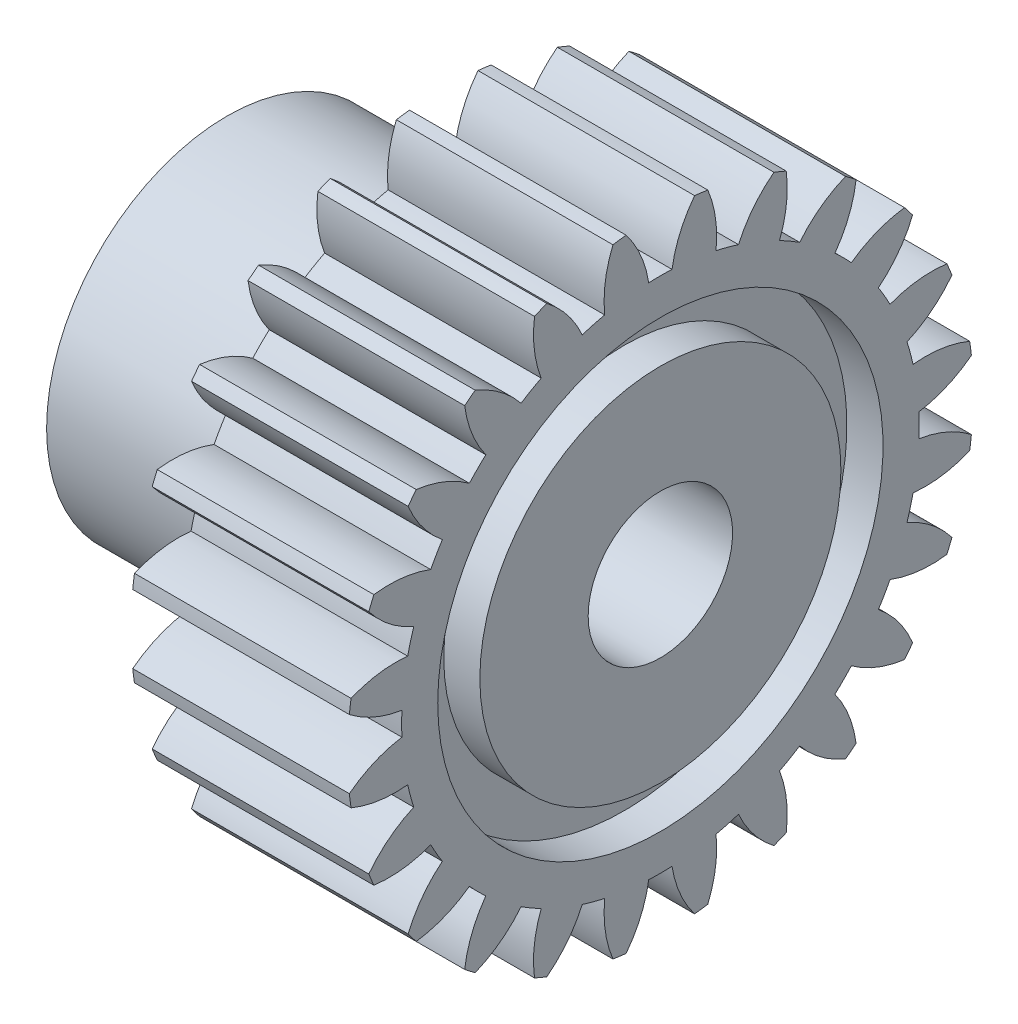
SolidWorks part; units mm, degrees
ref_plane "Plane1" through (0, 0, 0) normal (0, 0, 1) x (1, 0, 0)
ref_plane "Plane2" through (0, 0, 0) normal (0, 1, 0) x (1, 0, 0)
ref_plane "Plane3" through (0, 0, 0) normal (1, 0, 0) x (0, 0, -1)
other "Configuration Table"
sketch "HoldingSke" plane through (0, 0, 0) normal (0, 1, 0) x (1, 0, 0)
  line L0 (0, 0) -> (0.9135, -0.4067)
  line L1 (-15, 0) -> (100, 0) construction
  line L2 (0, 0) -> (-2.1039, 2.3779)
  line L3 (0, 0) -> (-11.863, 4.5341)
  line L4 (0, 0) -> (7.8894, 3.5126)
  line L5 (0, 0) -> (-16.8652, -6.2902)
  line L6 (0, 0) -> (-7.4607, -5.0337)
  line L7 (-2.1039, 2.3779) -> (1.7706, 19.956)
  line L8 (-76.2, 54.61) -> (-75.2, 54.61)
  line L9 (-71.009, 38.7566) -> (-53.1078, 45.2721)
  line L10 (-76.2, 71.12) -> (104.1128, 71.12)
  line L11 (0, 0) -> (-9, 0)
  line L12 (-76.2, 101.6) -> (-76.162, 101.6)
  line L13 (24.9733, 27.94) -> (52.9518, 28.4284)
  line L14 (24.9733, 27.94) -> (24.9743, 27.94)
  line L15 (24.9733, 27.94) -> (100.4006, 29.5858)
  line L16 (-63.627, -1) -> (-12.827, -1)
  circle A0 centre (0, 0) radius 3
  circle A1 centre (0, 0) radius 7.5
  circle A2 centre (0, 0) radius 7.5
  circle A3 centre (0, 0) radius 3
  dimension "Num_teeth" = 24
  dimension "Pitch_radius" = 180.3128
  dimension "Width" = 9
  dimension "Thickness" = 9
sketch "BasProSke" plane through (0, 0, 0) normal (0, 1, 0) x (1, 0, 0)
  line L0 (-10, 0) -> (60, 0) construction
  line L1 (0, 0) -> (0, 13)
  line L2 (0, 0) -> (9, 0)
  line L3 (9, 0) -> (9, 13)
  line L4 (9, 13) -> (0, 13)
  dimension "Thickness" = 9
  dimension "Diameter" = 26
revolve "Base-Revolve" add sketch "BasProSke" angle 360 about L0
sketch "TooCutSke" plane through (0, 0, 0) normal (1, 0, 0) x (0, 0, -1)
  line L1 (0, 0) -> (0, 107) construction
  line L2 (0, 0) -> (-0.8513, 11.9698) construction
  line L3 (0, 0) -> (-3.127, 23.752) construction
  line L4 (-0.8513, 11.9698) -> (-1.5635, 11.876) construction
  arc A0 (0.4834, 10.7381) -> (-0.4834, 10.7381) centre (0, 0) ccw
  arc A1 (1.4409, 12.9455) -> (-1.4409, 12.9455) centre (0, 0) ccw
  circle A2 centre (0, 0) radius 12 construction
  circle A3 centre (0, 0) radius 11.2763 construction
  arc A4 (-0.4834, 10.7381) -> (-1.4409, 12.9455) centre (-5.2252, 9.9926) ccw
  arc A5 (1.4409, 12.9455) -> (0.4834, 10.7381) centre (5.2252, 9.9926) ccw
extrude "ToothCut" cut sketch "TooCutSke" along normal through all
fillet "Breaks" [suppressed] radius 0.02 tangent propagation no
fillet "RootFillets" [suppressed] radius 0.251
pattern_circular "TeethCuts" count 24 every 15 about axis through (-10, 0, 0) along (1, 0, 0) of "ToothCut", "RootFillets", "Breaks"
sketch "HubNeaOneSke" plane through (0, 0, 0) normal (-1, 0, 0) x (0, 0, 1)
  circle A0 centre (0, 0) radius 7.5
  dimension "Diameter" = 15
extrude "HubNearOne" add sketch "HubNeaOneSke" along normal blind 9.0001
sketch "HubNeaBotSke" plane through (0, 0, 0) normal (-1, 0, 0) x (0, 0, 1)
  circle A0 centre (0, 0) radius 7.5
  dimension "Diameter" = 15
extrude "HubNearBoth" [suppressed] add sketch "HubNeaBotSke" along normal blind 4.5
ref_plane "FarPln" through (9, 0, 0) normal (1, 0, 0) x (0, 0, -1)
sketch "HubFarSke" plane through (9, 0, 0) normal (1, 0, 0) x (0, 0, -1)
  circle A0 centre (0, 0) radius 7.5
  dimension "Diameter" = 15
extrude "HubFar" [suppressed] add sketch "HubFarSke" along normal blind 4.5
sketch "BorSke" plane through (0, 0, 0) normal (1, 0, 0) x (0, 0, -1)
  circle A0 centre (0, 0) radius 3
  dimension "Diameter" = 6
extrude "Bore" cut sketch "BorSke" along normal mid plane 36.0001
sketch "KeySke" plane through (0, 0, 0) normal (1, 0, 0) x (0, 0, -1)
  line L0 (-1, 0) -> (-1, 4)
  line L1 (-1, 4) -> (1, 4)
  line L2 (1, 4) -> (1, 0)
  line L3 (0, 0) -> (0, 34) construction
  line L4 (-1, 0) -> (1, 0)
  dimension "Width" = 2
extrude "Keyway" [suppressed] cut sketch "KeySke" along normal mid plane 36.0001
pattern_circular "Keyway2" [suppressed] count 2 every 90 about axis through (-10, 0, 0) along (1, 0, 0) reverse direction yes
sketch "Sketch1" plane through (0, 0, 0) normal (-1, 0, 0) x (0, 0, 1)
  circle A0 centre (0, 0) radius 9.25
  circle A1 centre (0, 0) radius 7.5 construction
  circle A2 centre (0, 0) radius 7.5
  dimension "D1" = 18.5
extrude "Cut-Extrude1" cut sketch "Sketch1" against normal blind 1.5
extrude "Cut-Extrude2" cut sketch "Sketch1<2>" along normal blind 1.5 from surface starting at face at (9, 0, 3)
sketch "Sketch1<2>" plane through (0, 0, 0) normal (-1, 0, 0) x (0, 0, 1) same geometry as "Sketch1"
hole_wizard "CSK for M2.5 Countersunk Flat Head Screw1" positions "3DSketch1" profile "Sketch3" countersink size "M2.5" standard "ISO" end condition up to next
sketch3d "3DSketch1"
  point P0 (-2.7274, 0.7222, -7.4652)
sketch "Sketch3" plane through (-2.7274, 0.7222, -7.4652) normal (1, 0, 0) x (0, 0.9954, 0.0963)
  line L0 (0, 0) -> (0, 4.5)
  line L1 (0, 4.5) -> (1.35, 4.5)
  line L2 (1.35, 4.5) -> (1.35, 1.4)
  line L3 (1.35, 1.4) -> (2.75, 0)
  line L5 (2.75, 0) -> (0, 0)
  line L6 (-1.35, 1.4) -> (-2.75, 0) construction
  line L11 (0, -6.35) -> (0, 107.95) construction
  dimension "Thru Hole Dia." = 2.7
  dimension "Thru Hole Depth" = 4.5
  dimension "Near C'Sink Dia." = 5.5
  dimension "Near C'Sink Angle" = 90
equation "' \"Module@HoldingSke\" = 6.35"
equation "' \"Num_teeth@HoldingSke\" = 12"
equation "' \"Ap@HoldingSke\" =  20"
equation "' \"Ap@HoldingSke\" = 20"
equation "' \"Width@HoldingSke\" = 0.5 * 25.4"
equation "' \"Hub_dia@HoldingSke\"= 1 * 25.4"
equation "' \"Hub_dia@HoldingSke\" = 1 * 25.4"
equation "' \"Overall_len@HoldingSke\" = 1.0 * 25.4"
equation "' \"Bore@HoldingSke\" = 0.75 * 25.4"
equation "' \"T_dim@HoldingSke\" = 0.1 * 25.4"
equation "' \"Width@KeySke\" = 0.25 * 25.4"
equation "' \"Show_teeth@HoldingSke\" = 13"
equation "' \"Backlash@HoldingSke\" = 0.009 * 25.4"
equation "' \"Addendum_fac@HoldingSke\" = 1.0"
equation "' \"Dedendum_fac@HoldingSke\" = 1.25"
equation "' \"Dedendum_add@HoldingSke\" = 0.00005 * 25.4"
equation "' \"Clearance_fac@HoldingSke\" = 0.25"
equation "\"Pitch@HoldingSke\" = 1 / \"Module@HoldingSke\""
equation "\"Overcut_dia@TooCutSke\" = (\"Num_teeth@HoldingSke\" + 2 * \"Addendum_fac@HoldingSke\") / \"Pitch@HoldingSke\" + 0.002 * 25.4"
equation "\"Pitch_dia@TooCutSke\" = \"Num_teeth@HoldingSke\" / \"Pitch@HoldingSke\""
equation "\"Base_dia@TooCutSke\" = \"Num_teeth@HoldingSke\" / \"Pitch@HoldingSke\" * cos((\"Ap@HoldingSke\"  * 3.14159265 / 180))"
equation "\"Root_dia@TooCutSke\" = (\"Num_teeth@HoldingSke\" + 2) / \"Pitch@HoldingSke\" - 2 * (\"Addendum_fac@HoldingSke\" + \"Dedendum_fac@HoldingSke\") / \"Pitch@HoldingSke\" - \"Dedendum_add@HoldingSke\" * 2"
equation "\"Half_ang@TooCutSke\" = 180 / \"Num_teeth@HoldingSke\""
equation "\"Half_CT@TooCutSke\" = \"Num_teeth@HoldingSke\" / \"Pitch@HoldingSke\" * sin((3.14159265 / 2 / \"Num_teeth@HoldingSke\")) / 2 - 7 * \"Backlash@HoldingSke\" / 4"
equation "\"Flank_rad@TooCutSke\" = \"Num_teeth@HoldingSke\" / \"Pitch@HoldingSke\" / 5"
equation "\"Radius@RootFillets\" = \"Clearance_fac@HoldingSke\" / \"Pitch@HoldingSke\" + \"Dedendum_add@HoldingSke\""
equation "\"Break_rad@Breaks\" = 0.02 / \"Pitch@HoldingSke\""
equation "\"Thickness@HoldingSke\" = \"Width@HoldingSke\""
equation "\"OAL@HoldingSke\" = \"Thickness@HoldingSke\""
equation "\"MHD@HoldingSke\" = (\"Num_teeth@HoldingSke\" + 2) / \"Pitch@HoldingSke\" - 2 * (\"Addendum_fac@HoldingSke\" + \"Dedendum_fac@HoldingSke\")  / \"Pitch@HoldingSke\" - \"Dedendum_add@HoldingSke\" * 2"
equation "\"MBD@HoldingSke\" = (\"Num_teeth@HoldingSke\" + 2) / \"Pitch@HoldingSke\" - 2 * (\"Addendum_fac@HoldingSke\" + \"Dedendum_fac@HoldingSke\")  / \"Pitch@HoldingSke\" - \"Dedendum_add@HoldingSke\" * 2 - 0.002 * 25.4"
equation "\"MHD@HoldingSke\" = ((sgn( \"MHD@HoldingSke\" - \"Hub_dia@HoldingSke\" )-1)*( \"MHD@HoldingSke\" - \"Hub_dia@HoldingSke\" ))/-2+ \"Hub_dia@HoldingSke\""
equation "\"MBD@HoldingSke\" = ((sgn( \"MBD@HoldingSke\" - \"Bore@HoldingSke\" )-1)*( \"MBD@HoldingSke\" - \"Bore@HoldingSke\" ))/-2+ \"Bore@HoldingSke\""
equation "\"OAL@HoldingSke\" = ((sgn( \"OAL@HoldingSke\" - \"Overall_len@HoldingSke\" )+1)*( \"OAL@HoldingSke\" - \"Overall_len@HoldingSke\" ))/2 + \"Overall_len@HoldingSke\" + 0.000002 * 25.4"
equation "\"Num_teeth@TeethCuts\" = int( \"Show_teeth@HoldingSke\" ) + 1"
equation "\"Num_teeth@TeethCuts\" = ((sgn( \"Num_teeth@TeethCuts\" - \"Num_teeth@HoldingSke\" )-1)*( \"Num_teeth@TeethCuts\" - \"Num_teeth@HoldingSke\" ))/-2+ \"Num_teeth@HoldingSke\""
equation "\"Num_teeth@TeethCuts\" = ((sgn( \"Num_teeth@TeethCuts\" - 2.0)+1)*( \"Num_teeth@TeethCuts\" - 2.0))/2 +2.0"
equation "\"Angle@TeethCuts\" = 360.0 / \"Num_teeth@HoldingSke\""
equation "\"Diameter@BasProSke\" = (\"Num_teeth@HoldingSke\" + 2 * \"Addendum_fac@HoldingSke\") / \"Pitch@HoldingSke\""
equation "\"Thickness@BasProSke\"  = \"Thickness@HoldingSke\""
equation "' \"Fillet_rad@BasProSke\" =  \"Thickness@HoldingSke\" * 0.05"
equation "' \"Fillet_rad@BasProSke\" = \"Thickness@HoldingSke\" * 0.05"
equation "\"MHD@HoldingSke\" = ((sgn( \"MHD@HoldingSke\" - \"Root_dia@TooCutSke\" )-1)*( \"MHD@HoldingSke\" - \"Root_dia@TooCutSke\" ))/-2+ \"Root_dia@TooCutSke\""
equation "\"Diameter@HubNeaOneSke\" = \"MHD@HoldingSke\""
equation "\"Length@HubNearOne\" = \"OAL@HoldingSke\" - \"Thickness@BasProSke\""
equation "\"Diameter@HubNeaBotSke\" = \"MHD@HoldingSke\""
equation "\"Length@HubNearBoth\" = ( \"OAL@HoldingSke\" - \"Thickness@BasProSke\" ) / 2.0"
equation "\"Thickness@FarPln\" = \"Thickness@BasProSke\""
equation "\"Diameter@HubFarSke\" = \"MHD@HoldingSke\""
equation "\"Length@HubFar\" = ( \"OAL@HoldingSke\" - \"Thickness@BasProSke\" ) / 2.0"
equation "\"Diameter@BorSke\" = \"MBD@HoldingSke\""
equation "\"D1@Bore\" = \"OAL@HoldingSke\" * 2.0"
equation "\"D1@Keyway\" = \"OAL@HoldingSke\" * 2.0"
equation "\"Offset@KeySke\" = \"T_dim@HoldingSke\" + \"MBD@HoldingSke\" / 2.0"
